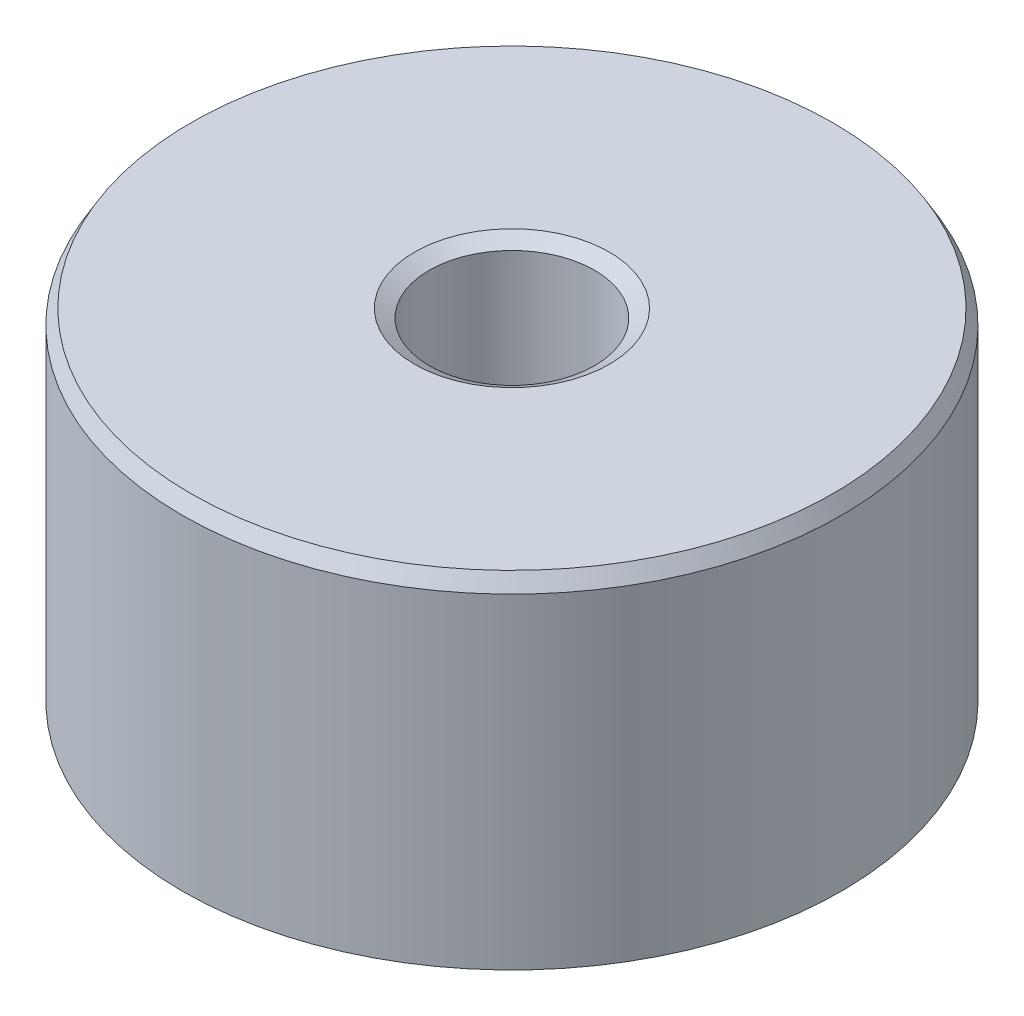
SolidWorks part; units mm, degrees
ref_plane "Front Plane" through (0, 0, 0) normal (0, 0, 1) x (1, 0, 0)
ref_plane "Top Plane" through (0, 0, 0) normal (0, 1, 0) x (1, 0, 0)
ref_plane "Right Plane" through (0, 0, 0) normal (1, 0, 0) x (0, 0, -1)
sketch "Sketch1" plane through (0, 0, 0) normal (0, 1, 0) x (1, 0, 0)
  circle A0 centre (0, 0) radius 5
  dimension "SLEEVE_OD" = 10
extrude "Boss-Extrude1" add sketch "Sketch1" along normal blind 5.2882
sketch "Sketch2" plane through (0, 0, 0) normal (0, 1, 0) x (1, 0, 0)
  circle A0 centre (0, 0) radius 1.2546
  dimension "BORE_D" = 2.5093
extrude "Cut-Extrude1" cut sketch "Sketch2" along normal through all
chamfer "Chamfer1" distance 0.2219 angle 30 4 edges at (0, 5.2882, 1.2546) (0, 0, 1.2546) (0, 0, 5) (0, 5.2882, 5) first distance on face at (0, 5.2882, 1.2546) first distance on face at (0, 0, 1.2546) first distance on face at (0, 5.2882, 5)
